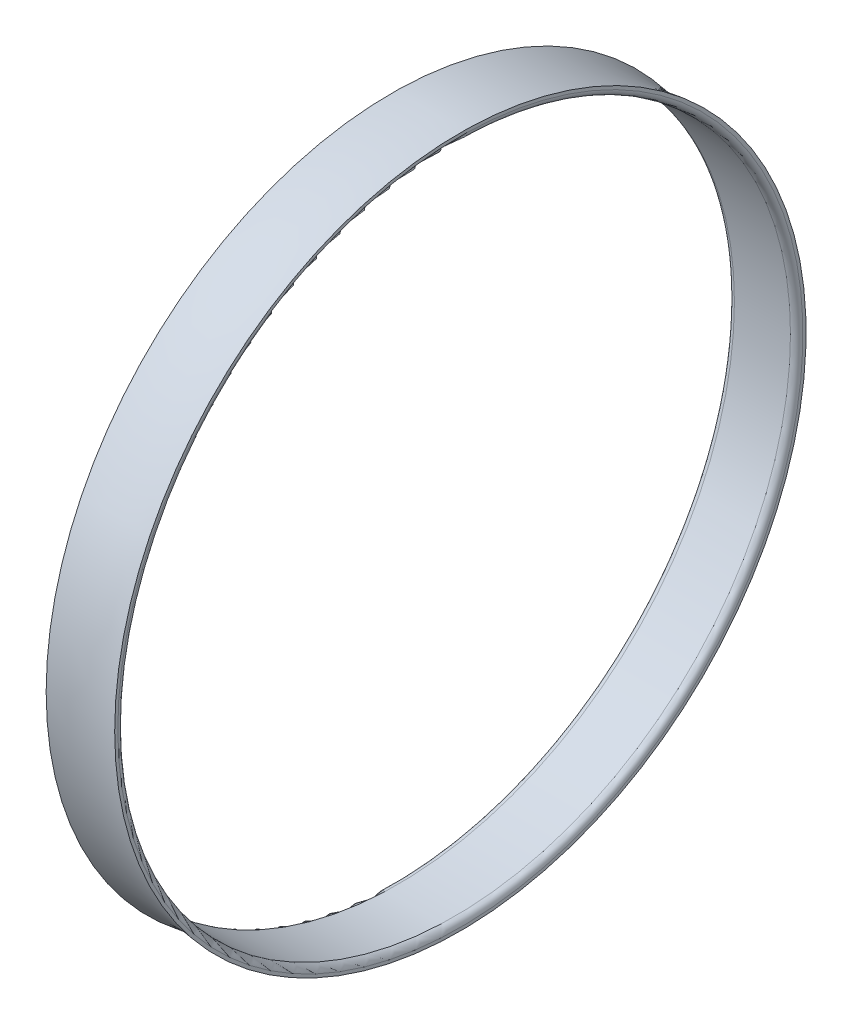
SolidWorks part; units mm, degrees
ref_plane "Płaszczyzna przednia" through (0, 0, 0) normal (0, 0, 1) x (1, 0, 0)
ref_plane "Płaszczyzna górna" through (0, 0, 0) normal (0, 1, 0) x (1, 0, 0)
ref_plane "Płaszczyzna prawa" through (0, 0, 0) normal (1, 0, 0) x (0, 0, -1)
sketch "Szkic1" plane through (0, 0, 0) normal (0, 0, 1) x (1, 0, 0)
  line L1 (5.7856, 53.9972) -> (14.7856, 53.9972)
  line L3 (-59.6339, 0) -> (89.1799, 0) construction
  line L15 (4.7856, 58.8508) -> (4.7856, 52.4763) construction
  line L16 (15.7856, 56.7161) -> (15.7856, 49.8699) construction
  line L17 (4.7856, 55.5) -> (4.7856, 54.9972)
  line L18 (15.7856, 55.5) -> (15.7856, 54.9972)
  line L19 (4.7856, -55) -> (4.7856, 55) construction
  arc A0 (15.7856, 55.5) -> (4.7856, 55.5) centre (10.2856, 84.9915) cw
  arc A6 (4.7856, 54.9972) -> (5.7856, 53.9972) centre (5.7856, 54.9972) ccw
  arc A7 (14.7856, 53.9972) -> (15.7856, 54.9972) centre (14.7856, 54.9972) ccw
  dimension "D1" = 30
  dimension "D2" = 55.5
  dimension "D3" = 11
  dimension "D4" = 0.5028
  dimension "D5" = 9
revolve "Obrót1" add sketch "Szkic1" angle 360 about L3
